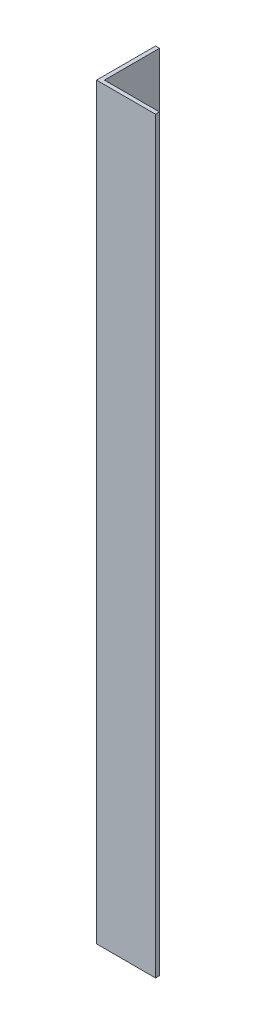
SolidWorks part; units mm, degrees
material "1060 Сплав"
ref_plane "Спереди" through (0, 0, 0) normal (0, 0, 1) x (1, 0, 0)
ref_plane "Сверху" through (0, 0, 0) normal (0, 1, 0) x (1, 0, 0)
ref_plane "Справа" through (0, 0, 0) normal (1, 0, 0) x (0, 0, -1)
sketch "Эскиз1" plane through (0, 0, 0) normal (0, 1, 0) x (1, 0, 0)
  line L0 (0, 0) -> (0, 15)
  line L1 (0, 15) -> (1, 15)
  line L2 (1, 15) -> (1, 1)
  line L3 (1, 1) -> (15, 1)
  line L4 (15, 1) -> (15, 0)
  line L5 (15, 0) -> (0, 0)
  dimension "D1" = 1
  dimension "D2" = 15
extrude "Бобышка-Вытянуть1" add sketch "Эскиз1" along normal blind 190
sketch "Эскиз2" plane through (1, 0, 0) normal (1, 0, 0) x (0, 0, -1)
  line L0 (8, 190) -> (8, 0) construction
  line L1 (1, 190) -> (15, 190) construction
  line L2 (1, 0) -> (15, 0) construction
  circle A0 centre (8, 179.5) radius 2.25
  dimension "D1" = 10.5
  dimension "D2" = 4.5
extrude "Вырез-Вытянуть1" cut sketch "Эскиз2" against normal through all
